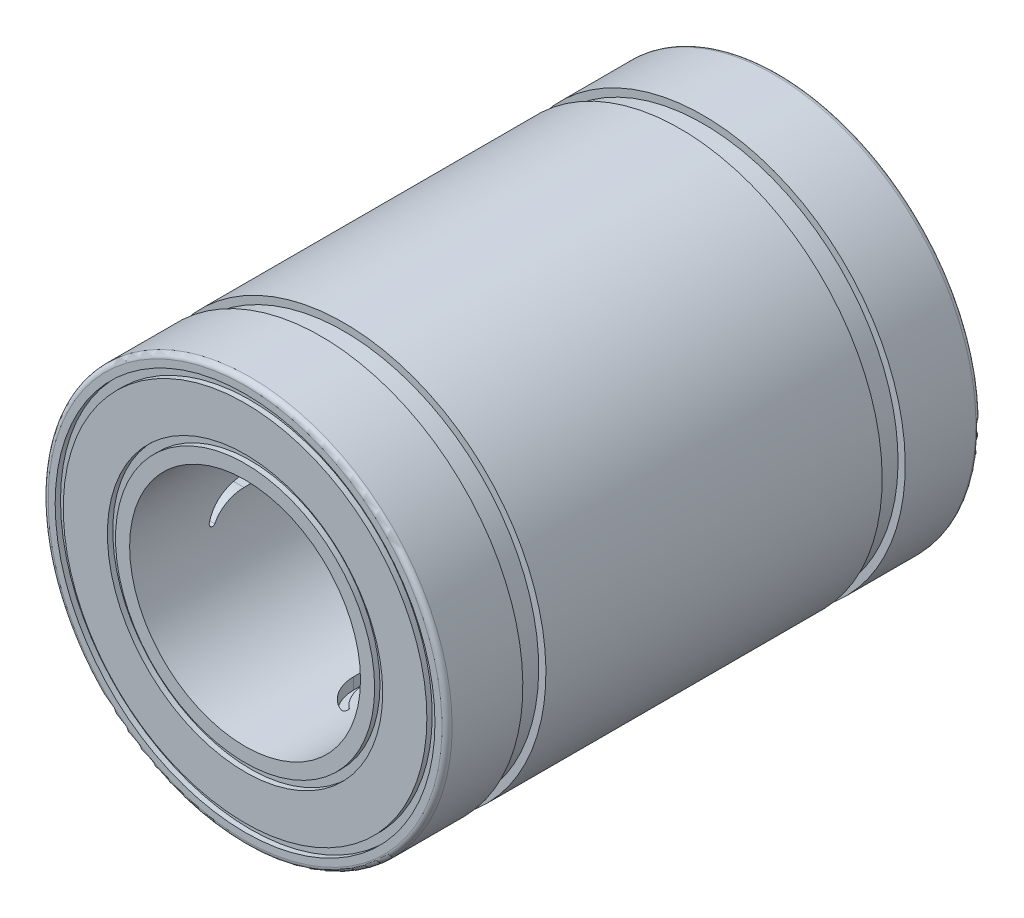
SolidWorks part; units mm, degrees
note: '?' marks a value the reader was unsure of.
material "Alloy Steel (SS)"
ref_plane "Front Plane" through (0, 0, 0) normal (0, 0, 1) x (1, 0, 0)
ref_plane "Top Plane" through (0, 0, 0) normal (0, 1, 0) x (1, 0, 0)
ref_plane "Right Plane" through (0, 0, 0) normal (1, 0, 0) x (0, 0, -1)
sketch "Sketch2" plane through (0, 0, 0) normal (1, 0, 0) x (0, 0, -1)
  line L0 (-18.5, 0) -> (18.5, 0) construction
  line L1 (-18.5, 8) -> (18.5, 8) construction
  line L2 (-18.5, 8) -> (-18.5, 14) construction
  line L3 (-18.5, 14) -> (-13.25, 14) construction
  line L4 (-13.25, 14) -> (-13.25, 13.5) construction
  line L5 (-13.25, 13.5) -> (-11.65, 13.5) construction
  line L6 (-11.65, 13.5) -> (-11.65, 14) construction
  line L7 (-11.65, 14) -> (11.65, 14) construction
  line L8 (11.65, 14) -> (11.65, 13.5) construction
  line L9 (11.65, 13.5) -> (13.25, 13.5) construction
  line L10 (13.25, 13.5) -> (13.25, 14) construction
  line L11 (13.25, 14) -> (18.5, 14) construction
  line L12 (18.5, 14) -> (18.5, 8) construction
  line L13 (-18.5, 8.5) -> (18.5, 8.5) construction
  line L14 (0, 14) -> (0, 0) construction
  point P4 (0, 0)
  dimension "Length" = 37
  dimension "ID" = 16
  dimension "Supplier B" = 26.5
  dimension "Supplier W" = 1.6
  dimension "OD" = 28
  dimension "Supplier D1" = 27
  dimension "Ball Diameter" = 0.5
sketch "Sketch4" plane through (0, 0, 0) normal (1, 0, 0) x (0, 0, -1)
  line L0 (-18.5, 8) -> (-18.5, 14)
  line L1 (-18.5, 14) -> (-13.25, 14)
  line L2 (-13.25, 14) -> (-13.25, 13.5)
  line L3 (-13.25, 13.5) -> (-11.65, 13.5)
  line L4 (-11.65, 13.5) -> (-11.65, 14)
  line L5 (-11.65, 14) -> (11.65, 14)
  line L6 (11.65, 14) -> (11.65, 13.5)
  line L7 (11.65, 13.5) -> (13.25, 13.5)
  line L8 (13.25, 13.5) -> (13.25, 14)
  line L9 (13.25, 14) -> (18.5, 14)
  line L10 (18.5, 14) -> (18.5, 8)
  line L11 (18.5, 8) -> (-18.5, 8)
revolve "Revolve1" add sketch "Sketch4" angle 360 about L0
sketch "Sketch5" plane through (0, 0, 18.5) normal (0, 0, 1) x (1, 0, 0)
  line L0 (0, 13.16) -> (0, 12.6) construction
  line L1 (0, 12.6) -> (0, 7.155) construction
  line L2 (0, 9.54) -> (0, 8.98) construction
  circle A0 centre (0, 0) radius 14 construction
  circle A1 centre (0, 0) radius 13.16
  circle A3 centre (0, 0) radius 12.6
  circle A4 centre (0, 0) radius 8.98
  circle A6 centre (0, 0) radius 8 construction
  circle A8 centre (0, 0) radius 9.54
  dimension "D1" = 0.84
  dimension "D2" = 0.56
  dimension "D3" = 0.98
extrude "Cut-Extrude1" cut sketch "Sketch5" against normal blind 0.37 contours A8 A4 | A1 A3
mirror "Mirror1" about plane through (0, 0, 0) normal (0, 0, 1) of "Cut-Extrude1"
sketch "Sketch7" plane through (0, 0, 0) normal (1, 0, 0) x (0, 0, -1)
  line L1 (13.25, 0) -> (-13.25, 0) construction
  line L2 (-13.25, 0) -> (-13.25, -2.6667) construction
  line L3 (13.25, 0) -> (13.25, -2.6667) construction
  line L6 (10.5833, 0.41) -> (-10.5833, 0.41)
  line L7 (10.5833, -0.41) -> (-10.5833, -0.41)
  line L8 (0, 0.41) -> (0, -0.41) construction
  circle A4 centre (0, 0) radius 0.4 construction
  arc A7 (-13.25, -2.6667) -> (-10.5833, 0) centre (-10.5833, -2.6667) cw construction
  arc A8 (13.25, -2.6667) -> (10.5833, 0) centre (10.5833, -2.6667) ccw construction
  circle A9 centre (0, 0) radius 0.41 construction
  circle A10 centre (-13.25, -2.6667) radius 0.41 construction
  arc A11 (-13.0775, -1.2568) -> (-12.7354, -1.4568) centre (-12.8927, -1.3333) ccw
  arc A12 (-12.7354, -1.4568) -> (-10.5833, -0.41) centre (-10.5833, -3.1456) cw
  arc A13 (-13.0775, -1.2568) -> (-10.5833, 0.41) centre (-10.5833, -2.2895) cw
  arc A14 (13.0775, -1.2568) -> (10.5833, 0.41) centre (10.5833, -2.2895) ccw
  arc A15 (12.7354, -1.4568) -> (10.5833, -0.41) centre (10.5833, -3.1456) ccw
  arc A16 (13.0775, -1.2568) -> (12.7354, -1.4568) centre (12.8927, -1.3333) cw
  point P5 (0, 0)
  point P8 (-60.3, -25)
  point P13 (-81.55, -25)
  point P16 (-60.3, -3.75)
  point P17 (60.3, -3.75)
  point P19 (60.3, -25)
  point P20 (81.55, -25)
  point P21 (-60.3, -25)
  point P22 (-89.05, -25)
  point P23 (-60.3, 3.75)
  point P24 (60.3, 3.75)
  point P25 (60.3, -25)
  point P26 (89.05, -25)
  point P30 (0, -0.41)
  point P33 (0, 0.41)
  point P34 (-12.8927, -1.3333)
  dimension "D1" = 0.8
  dimension "D6" = 0.4
  dimension "D2" = 26.5
  dimension "D3" = 2.6667
  dimension "D5" = 1.3333
  dimension "D4" = 0.01
extrude "Cut-Extrude3" cut sketch "Sketch7" against normal offset from surface (8.7098 mm away) 0.8
ref_plane "Plane2" through (0, 0, -10.5833) normal (0, 0, 1) x (1, 0, 0)
sketch "Sketch8" plane through (0, 0, -10.5833) normal (0, 0, 1) x (1, 0, 0)
  line L0 (0, 0) -> (-8, 0) construction
  line L1 (-8, 0) -> (-8.8, 0) construction
  line L3 (0, -8.4) -> (0, 8.4) construction
  line L4 (-8.4, 0.41) -> (-8.4, -0.41)
  line L5 (-8.35, 0.41) -> (-8.4, 0.41)
  line L6 (-8.35, 0.41) -> (-8.35, 0.39)
  line L7 (-8.35, 0.29) -> (-8.35, -0.29) construction
  line L9 (-8.4, 0.29) -> (-8.4, -0.29) construction
  line L10 (-8.35, -0.41) -> (-8.35, -0.39)
  line L11 (-8.35, -0.41) -> (-8.4, -0.41)
  line L12 (-8.7904, 0.41) -> (-7.9895, 0.41) construction
  line L13 (-8.7904, 0.41) -> (-7.9895, 0.41) construction
  arc A0 (-8.7904, 0.41) -> (-8.7098, -1.2568) centre (0, 0) ccw construction
  arc A1 (-7.9895, 0.41) -> (-7.9007, -1.2568) centre (0, 0) ccw construction
  arc A4 (-8.35, -0.39) -> (-8.35, 0.39) centre (-8.4, 0) ccw
  circle A5 centre (0, 0) radius 8.4 construction
  arc A6 (-8.7904, 0.41) -> (-8.7098, -1.2568) centre (0, 0) ccw construction
  arc A7 (-7.9895, 0.41) -> (-7.9007, -1.2568) centre (0, 0) ccw construction
  point P27 (-8.4, 0)
  dimension "D1" = 0.02
  dimension "D2" = 0.05
ref_plane "Plane1" through (-8.4, 0, 0) normal (1, 0, 0) x (0, 0, -1)
revolve "Revolve2" [suppressed] add sketch "Sketch8" angle 360 about L4
ref_axis "Axis1" through (0, 0, -18.5) along (0, 0, 1)?
pattern_circular "CirPattern3" count 4 over 360 about axis through (0, 0, 0) along (0, 0, 1) of "Cut-Extrude3"
pattern_circular "CirPattern5" [suppressed] count 4 over 360 about axis through (0, 0, -18.5) along (0, 0, 1)
pattern_linear "LPattern1" [suppressed] count 22 spacing 1
fillet "Fillet1" radius 0.35 2 edges at (0, -14, -18.5) (0, -14, 18.5)
sketch "SketchX" plane through (0, 0, 0) normal (0, 0, 1) x (1, 0, 0)
  line L0 (0, 8) -> (0, -8)
  line L1 (0, 14) -> (0, -14)
  point P4 (0, 0)
  point P8 (0, 0)
  dimension "D1" = 28
  dimension "D2" = 16
ref_axis "Center Axis 1" through (0, 0, -18.5) along (0, 0, 1)?
equation "\"Ball Diameter@Sketch2\"=(\"OD@Sketch2\"-\"Supplier D1@Sketch2\")/2"
equation "\"D1@CirPattern5\" = \"BearingChannels@CirPattern3\""
equation "\"D1@SketchX\" = \"OD@Sketch2\""
equation "\"D2@SketchX\" = \"ID@Sketch2\""
equation "\"D1@Sketch7\"=\"ID@Sketch2\"*.05"
equation "\"D2@Sketch7\"=\"Supplier B@Sketch2\""
equation "\"D3@Sketch7\"=\"ID@Sketch2\"/6"
equation "\"D5@Sketch7\"=\"D3@Sketch7\"/2"
equation "\"D6@Sketch7\"=\"D1@Sketch7\"/2"
equation "\"D1@Cut-Extrude3\"=\"D1@Sketch7\""
equation "\"D3@LPattern1\"=\"D1@Sketch7\"*1.25"
equation "\"D5@LPattern1\"=\"D3@LPattern1\"/2"
equation "\"D1@Sketch5\"=\"OD@Sketch2\"*.03"
equation "\"D2@Sketch5\"=\"OD@Sketch2\"*.02"
equation "\"D3@Sketch5\"=\"OD@Sketch2\"*.035"
equation "\"D1@Cut-Extrude1\"=\"Length@Sketch2\"*.01"
equation "\"D1@Fillet1\"=\"OD@Sketch2\"*.0125"
